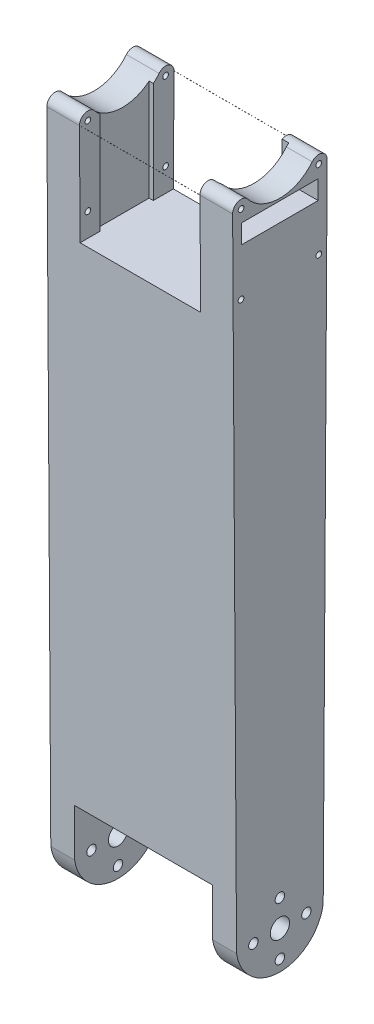
SolidWorks part; units mm, degrees
ref_plane "Front Plane" through (0, 0, 0) normal (0, 0, 1) x (1, 0, 0)
ref_plane "Top Plane" through (0, 0, 0) normal (0, 1, 0) x (1, 0, 0)
ref_plane "Right Plane" through (0, 0, 0) normal (1, 0, 0) x (0, 0, -1)
sketch "Sketch1" plane through (0, 0, 0) normal (1, 0, 0) x (0, 0, -1)
  line L0 (55.88, 0) -> (-55.88, 0) construction
  line L1 (-32.73, 0) -> (12.5, 0) construction
  line L2 (-32.73, 0) -> (-32.73, -36.5) construction
  line L3 (-32.73, -36.5) -> (12.5, -36.5) construction
  line L4 (12.5, 0) -> (12.5, -36.5) construction
  line L5 (0, 38.1) -> (0, 215.9) construction
  line L6 (-50.8, 0) -> (50.8, 0) construction
  line L7 (-50.8, 0) -> (-50.8, -50.8) construction
  line L8 (-50.8, -50.8) -> (50.8, -50.8) construction
  line L9 (50.8, 0) -> (50.8, -50.8) construction
  line L10 (0, 55.88) -> (0, -55.88) construction
  line L11 (0, 215.9) -> (-75.29, 422.7577) construction
  line L12 (-67.0833, 436.5088) -> (-90.4159, 428.0165) construction
  line L13 (12.415, 180.785) -> (-12.415, 180.785) construction
  line L18 (12.415, 180.785) -> (12.415, 226.015) construction
  line L19 (-12.415, 180.785) -> (-12.415, 226.015) construction
  line L20 (12.415, 226.015) -> (-12.415, 226.015) construction
  line L21 (0, 215.9) -> (0, 180.785) construction
  line L22 (0, 203.4) -> (-12.415, 203.4) construction
  line L27 (-67.0833, 436.5088) -> (-51.6137, 394.0065) construction
  line L28 (-90.4159, 428.0165) -> (-74.9463, 385.5142) construction
  line L29 (-51.6137, 394.0065) -> (-74.9463, 385.5142) construction
  line L30 (-59.3485, 415.2577) -> (-82.6811, 406.7653) construction
  line L31 (-75.29, 422.7577) -> (-133.6626, 471.7381) construction
  line L33 (-12.415, 50.6) -> (12.415, 50.6) construction
  line L34 (-12.415, 50.6) -> (-12.415, 5.37) construction
  line L35 (-12.415, 5.37) -> (12.415, 5.37) construction
  line L36 (12.415, 50.6) -> (12.415, 5.37) construction
  circle A0 centre (0, 38.1) radius 3 construction
  circle A1 centre (0, 215.9) radius 3 construction
  circle A3 centre (-75.29, 422.7577) radius 3 construction
  point P6 (-10.115, -36.5)
  point P9 (0, -50.8)
  point P25 (-12.5, 38.1)
  point P27 (0, 203.4)
  point P42 (-63.28, 389.7604)
  point P47 (0, 5.37)
  dimension "D15" = 6
  dimension "D8" = 0
  dimension "D12" = 12.5
  dimension "D1" = 36.5
  dimension "D2" = 45.23
  dimension "D3" = 101.6
  dimension "D4" = 50.8
  dimension "D5" = 38.1
  dimension "D6" = 177.8
  dimension "D7" = 220.1333
  dimension "D9" = 24.83
  dimension "D10" = 12.5
  dimension "D11" = 12.5
  dimension "D13" = 76.2
  dimension "D14" = 160
  dimension "D16" = 12.5
  dimension "D17" = 150
  dimension "D18" = 12.5
sketch "Sketch2" plane through (0, 0, 0) normal (0, 0, 1) x (1, 0, 0)
  line L6 (55.88, 0) -> (-55.88, 0) construction
  line L7 (-50.8, 0) -> (50.8, 0) construction
  line L8 (-50.8, 0) -> (-50.8, -50.8) construction
  line L9 (-50.8, -50.8) -> (50.8, -50.8) construction
  line L10 (50.8, 0) -> (50.8, -50.8) construction
  dimension "D1" = 101.6
sketch "Sketch3" plane through (0, 0, 0) normal (1, 0, 0) x (0, 0, -1)
  line L0 (-11.4298, 38.0297) -> (-12.4725, 207.5865)
  line L1 (-10.25, 9.1002) -> (10.25, 9.1002) construction
  line L3 (-10.25, 186.9002) -> (10.25, 186.9002) construction
  line L4 (0, 215.9) -> (-75.29, 422.7577) construction
  line L5 (12.4725, 207.5865) -> (11.4298, 38.0297)
  circle A0 centre (0, 38.1) radius 10
  circle A1 centre (-10.25, 9.1002) radius 0.7501
  circle A2 centre (10.25, 9.1002) radius 0.7501
  circle A3 centre (10.25, 29.8002) radius 0.7501
  circle A4 centre (-10.25, 29.8002) radius 0.7501
  circle A5 centre (0, 45.1) radius 1.2501
  circle A6 centre (7, 38.1) radius 1.2501
  circle A7 centre (0, 31.1) radius 1.2501
  circle A8 centre (-7, 38.1) radius 1.2501
  circle A9 centre (-10.25, 186.9002) radius 0.7501
  circle A10 centre (10.25, 186.9002) radius 0.7501
  circle A11 centre (10.25, 207.6001) radius 0.7501
  circle A12 centre (-10.25, 207.6001) radius 0.7501
  circle A13 centre (0, 215.9) radius 10 construction
  arc A14 (-8.5228, 208.9988) -> (8.5228, 208.9988) centre (0, 215.9) ccw
  arc A16 (8.5228, 208.9988) -> (12.4725, 207.5865) centre (10.25, 207.6001) cw
  arc A17 (-11.4298, 38.0297) -> (11.4298, 38.0297) centre (0, 38.1) ccw
  circle A18 centre (0, 38.1) radius 2.54
  arc A19 (-8.5228, 208.9988) -> (-12.4725, 207.5865) centre (-10.25, 207.6001) ccw
  arc A20 (11.4298, 38.0297) -> (-11.4298, 38.0297) centre (0, 39.6431) cw
  point P5 (0, 186.9002)
  point P16 (0, 9.1002)
  dimension "D1" = 1.5001
  dimension "D9" = 20
  dimension "D12" = 2.5001
  dimension "D13" = 20.7
  dimension "D16" = 0
  dimension "D17" = 5.08
  dimension "D18" = 11.43
  dimension "D19" = 2.2225
  dimension "D4" = 13.189
  dimension "D5" = 28.9998
  dimension "D6" = 20.5001
  dimension "D7" = 20.7
  dimension "D8" = 28.9998
  dimension "D10" = 7
  dimension "D14" = 20.5
  dimension "D15" = 13.189
  dimension "D2" = 2
  dimension "D3" = 2
  dimension "D11" = 4
extrude "Boss-Extrude1" add sketch "Sketch3" along normal blind 24.511 and the other way blind 24.511 contours A17 L5 A16 A14 A19 L0
extrude "Cut-Extrude3" cut sketch "Sketch3<4>" against normal through all and the other way through all contours A8 | A5 | A6 | A7 | A9 | A10 | A11 | A12 | A18
sketch "Sketch3<4>" plane through (0, 0, 0) normal (1, 0, 0) x (0, 0, -1) same geometry as "Sketch3"
sketch "Sketch4" plane through (0, 0, 0) normal (1, 0, 0) x (0, 0, -1)
  line L0 (-12.415, 50.6) -> (12.415, 50.6) construction
  line L1 (-11.5071, 50.6) -> (11.5071, 50.6)
  line L2 (-11.5071, 50.6) -> (-11.5071, 26.67)
  line L3 (-11.5071, 26.67) -> (11.5071, 26.67)
  line L4 (11.5071, 50.6) -> (11.5071, 26.67)
  line L5 (-11.4298, 38.0297) -> (-12.4725, 207.5865) construction
  line L6 (12.4725, 207.5865) -> (11.4298, 38.0297) construction
  line L8 (-12.4725, 180.7002) -> (12.4725, 180.7002)
  line L9 (-12.4725, 180.7002) -> (-12.4725, 209.8226)
  line L10 (-12.4725, 209.8226) -> (12.4725, 209.8226)
  line L11 (12.4725, 180.7002) -> (12.4725, 209.8226)
  arc A0 (-11.4298, 38.0297) -> (11.4298, 38.0297) centre (0, 38.1) ccw construction
  arc A2 (-8.5228, 208.9988) -> (-12.4725, 207.5865) centre (-10.25, 207.6001) ccw construction
  dimension "D1" = 6.2
extrude "Cut-Extrude4" cut sketch "Sketch4" against normal blind 18.2 and the other way blind 18.2 contours L4 L1 L2 L3 region at (0, 38.635, 0)
extrude "Cut-Extrude5" cut sketch "Sketch4<4>" against normal blind 15.9 and the other way blind 15.9 contours L8 L11 L10 L9 region at (0, 195.2614, 0)
sketch "Sketch4<4>" plane through (0, 0, 0) normal (1, 0, 0) x (0, 0, -1) same geometry as "Sketch4"
sketch "Sketch5" plane through (15.9, 0, 0) normal (-1, 0, 0) x (0, 0, 1)
  line L0 (-11.9981, 210.6001) -> (-11.9981, 208.7639)
  line L1 (-11.9981, 206.4364) -> (-11.9981, 184.2639)
  line L2 (-9.6037, 181.1021) -> (9.6037, 181.1021)
  line L3 (11.9981, 184.2639) -> (11.9981, 206.4364)
  line L4 (11.9981, 208.7639) -> (11.9981, 210.6001)
  line L5 (11.9981, 210.6001) -> (9.645, 210.6001)
  line L6 (6.5, 207.0195) -> (6.5, 204.3501)
  line L7 (6.5, 204.3501) -> (10.1, 204.3501)
  line L8 (10.1, 204.3501) -> (10.1, 199.3501)
  line L9 (10.1, 199.3501) -> (9.2, 199.3501)
  line L10 (9.2, 199.3501) -> (9.2, 186.0001)
  line L11 (9.2, 186.0001) -> (-9.2, 186.0001)
  line L12 (-9.2, 186.0001) -> (-9.2, 199.3501)
  line L13 (-9.2, 199.3501) -> (-10.1, 199.3501)
  line L14 (-10.1, 199.3501) -> (-10.1, 204.3501)
  line L15 (-10.1, 204.3501) -> (-6.5, 204.3501)
  line L16 (-6.5, 204.3501) -> (-6.5, 207.0195)
  line L17 (-9.645, 210.6001) -> (-11.9981, 210.6001)
  line L19 (-10.1, 204.3501) -> (10.1, 204.3501)
  line L20 (-10.1, 204.3501) -> (-10.1, 199.3501)
  line L21 (-10.1, 199.3501) -> (10.1, 199.3501)
  line L22 (10.1, 204.3501) -> (10.1, 199.3501)
  line L23 (9.2, 186.0001) -> (-9.2, 186.0001)
  line L24 (9.2, 186.0001) -> (9.2, 199.3501)
  line L25 (9.2, 199.3501) -> (-9.2, 199.3501)
  line L26 (-9.2, 186.0001) -> (-9.2, 199.3501)
  line L27 (-9.2, 199.3501) -> (9.2, 199.3501)
  line L28 (-9.2, 199.3501) -> (-9.2, 210.6001)
  line L29 (-9.2, 210.6001) -> (9.2, 210.6001)
  line L30 (9.2, 199.3501) -> (9.2, 210.6001)
  arc A0 (-11.9981, 208.7639) -> (-11.9981, 206.4364) centre (-10.25, 207.6001) ccw
  arc A1 (-11.9981, 184.2639) -> (-9.6037, 181.1021) centre (-10.25, 183.1001) ccw
  arc A2 (9.6037, 181.1021) -> (11.9981, 184.2639) centre (10.25, 183.1001) ccw
  arc A3 (11.9981, 206.4364) -> (11.9981, 208.7639) centre (10.25, 207.6001) ccw
  arc A4 (6.5, 207.0195) -> (9.645, 210.6001) centre (0, 215.9001) ccw
  arc A5 (-9.645, 210.6001) -> (-6.5, 207.0195) centre (0, 215.9001) ccw
  arc M30 (12.4725, 207.6138) -> (8.5228, 208.9988) centre (10.25, 207.6001) ccw
  arc M31 (8.5228, 208.9988) -> (-8.5228, 208.9988) centre (0, 215.9) cw
  arc M32 (-8.5228, 208.9988) -> (-12.4725, 207.6138) centre (-10.25, 207.6001) ccw
extrude "Cut-Extrude6" cut sketch "Sketch5" against normal blind 18.2 contours L20 L19 L22 L21
extrude "Cut-Extrude7" cut sketch "Sketch5<3>" against normal blind 1.8 contours L21 L12 L11 L10 | A5 L16 L19 L6 A4 M32 M30 M31 | A5 L28 L19 L16 M32 | A4 L6 L7 L30 M30 region at (15.9, 206.3775, -8.0053) region at (15.9, 209.128, -8.6612) region at (15.9, 192.6751, 0) region at (15.9, 206.3775, 8.0053)
sketch "Sketch5<3>" plane through (15.9, 0, 0) normal (-1, 0, 0) x (0, 0, 1) same geometry as "Sketch5"
sketch "Sketch6" plane through (-15.9, 0, 0) normal (1, 0, 0) x (0, 0, -1)
  line L0 (-12.3071, 180.7002) -> (12.3071, 180.7002) construction
  line L1 (7, 180.7002) -> (-7, 180.7002)
  line L2 (7, 180.7002) -> (7, 209.8226)
  line L3 (7, 209.8226) -> (-7, 209.8226)
  line L4 (-7, 180.7002) -> (-7, 209.8226)
  arc A0 (-8.5228, 208.9988) -> (-12.4725, 207.6138) centre (-10.25, 207.6001) ccw construction
  point P6 (0, 180.7002)
  point P8 (0, 209.8226)
  dimension "D1" = 14
extrude "Cut-Extrude8" cut sketch "Sketch6" against normal blind 1.1
extrude "Cut-Extrude10" cut sketch "Sketch3<5>" against normal through all and the other way through all contours A17 A20 region at (0, 30.7364, 7.7377)
sketch "Sketch3<5>" plane through (0, 0, 0) normal (1, 0, 0) x (0, 0, -1) same geometry as "Sketch3"
